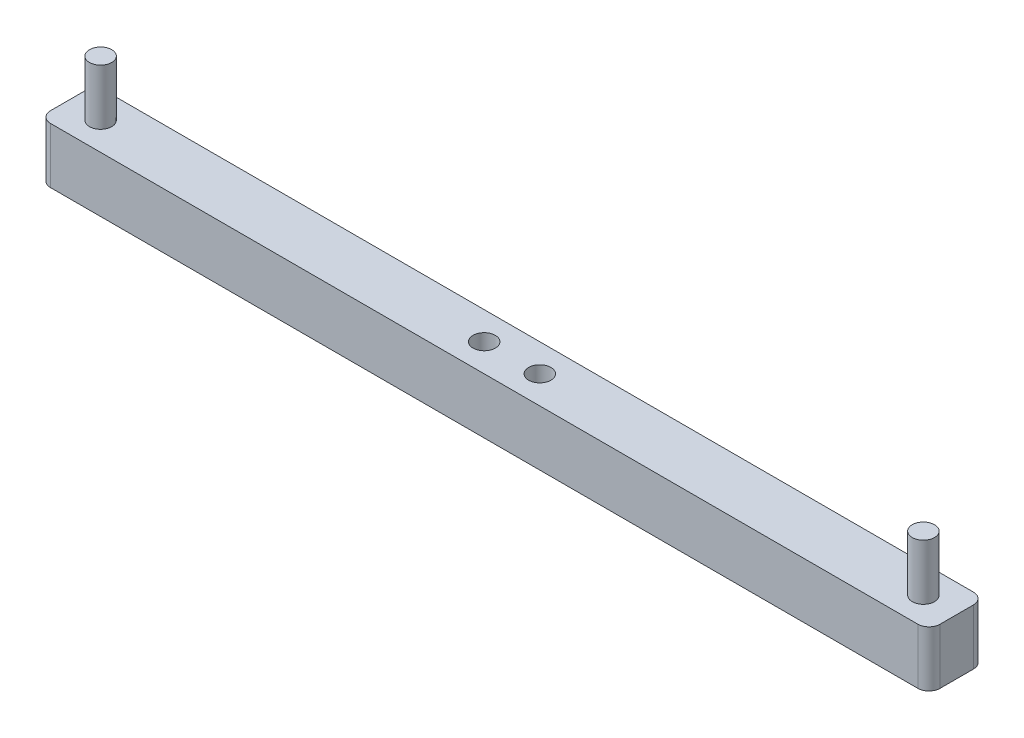
SolidWorks part; units mm, degrees
material "1060 Alloy"
ref_plane "Front Plane" through (0, 0, 0) normal (0, 0, 1) x (1, 0, 0)
ref_plane "Top Plane" through (0, 0, 0) normal (0, 1, 0) x (1, 0, 0)
ref_plane "Right Plane" through (0, 0, 0) normal (1, 0, 0) x (0, 0, -1)
sketch "Sketch1" plane through (0, 0, 0) normal (0, 1, 0) x (1, 0, 0)
  line L1 (-40, 2.5) -> (40, 2.5)
  line L2 (-40, 2.5) -> (-40, -2.5)
  line L3 (-40, -2.5) -> (40, -2.5)
  line L4 (40, 2.5) -> (40, -2.5)
  line L5 (-40, 2.5) -> (40, -2.5) construction
  line L6 (-40, -2.5) -> (40, 2.5) construction
  point P0 (0, 0)
  dimension "D1" = 80
  dimension "D2" = 5
extrude "Boss-Extrude1" add sketch "Sketch1" along normal blind 5
fillet "Fillet1" radius 1 2 edges at (-40, 2.5, -2.5) (-40, 2.5, 2.5)
fillet "Fillet2" radius 1 2 edges at (40, 2.5, -2.5) (40, 2.5, 2.5)
sketch "Sketch2" plane through (0, 5, 0) normal (0, 1, 0) x (1, 0, 0)
  line L0 (-40, 1.5) -> (-40, -1.5) construction
  line L1 (-39, -2.5) -> (39, -2.5) construction
  line L2 (40, -1.5) -> (40, 1.5) construction
  line L3 (39, 2.5) -> (-39, 2.5) construction
  line L4 (-2.5, 0) -> (2.5, 0) construction
  circle A0 centre (-37, 0) radius 1
  circle A1 centre (37, 0) radius 1
  circle A3 centre (-2.5, 0) radius 1
  circle A4 centre (2.5, 0) radius 1
  point P17 (0, 0)
  dimension "D1" = 2
  dimension "D6" = 2
  dimension "D7" = 5
  dimension "D8" = 2
  dimension "D9" = 2
  dimension "D2" = 3
  dimension "D3" = 2.5
  dimension "D4" = 3
  dimension "D5" = 2.5
extrude "Cut-Extrude1" cut sketch "Sketch2" against normal through all contours A4 | A3 region at (-2.5, 5, 0) region at (2.5, 5, 0)
extrude "Boss-Extrude2" add sketch "Sketch2<3>" along normal blind 5 contours A1 | A0 region at (37, 5, 0)
sketch "Sketch2<3>" plane through (0, 5, 0) normal (0, 1, 0) x (1, 0, 0) same geometry as "Sketch2"
